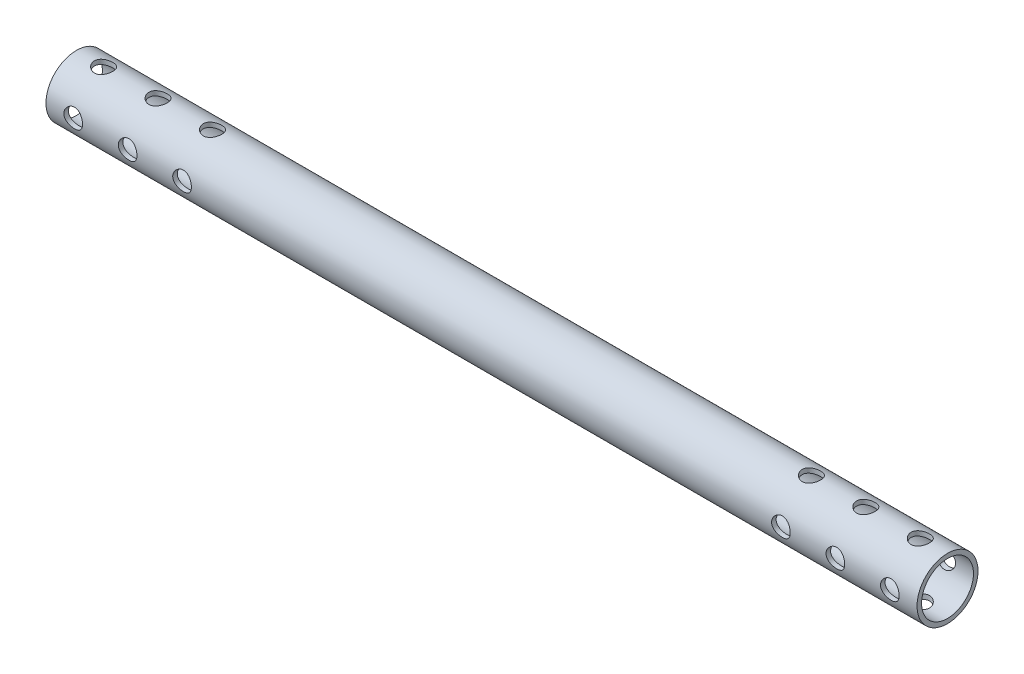
SolidWorks part; units mm, degrees
ref_plane "Front Plane" through (0, 0, 0) normal (0, 0, 1) x (1, 0, 0)
ref_plane "Top Plane" through (0, 0, 0) normal (0, 1, 0) x (1, 0, 0)
ref_plane "Right Plane" through (0, 0, 0) normal (1, 0, 0) x (0, 0, -1)
sketch "Sketch1" plane through (0, 0, 0) normal (1, 0, 0) x (0, 0, -1)
  circle A0 centre (0, 0) radius 10.668
  circle A1 centre (0, 0) radius 9.0805
  dimension "D1" = 1.5875
  dimension "D2" = 21.336
extrude "Boss-Extrude1" add sketch "Sketch1" along normal blind 304.8
ref_plane "Plane1" through (0, 0, 10) normal (0, 0, 1) x (1, 0, 0)
sketch "Sketch2" plane through (0, 0, 10) normal (0, 0, 1) x (1, 0, 0)
  line L0 (0, 0) -> (304.8, 0) construction
  line L1 (304.8, -10.668) -> (304.8, 10.668) construction
  line L2 (152.4, 10.668) -> (152.4, -10.668) construction
  line L3 (304.8, 10.668) -> (0, 10.668) construction
  circle A0 centre (9.525, 0) radius 3.2639
  circle A1 centre (28.575, 0) radius 3.2639
  circle A2 centre (47.625, 0) radius 3.2639
  circle A3 centre (295.275, 0) radius 3.2639
  circle A4 centre (276.225, 0) radius 3.2639
  circle A5 centre (257.175, 0) radius 3.2639
  point P15 (152.4, 0)
  dimension "D1" = 9.525
  dimension "D2" = 3
extrude "Cut-Extrude1" cut sketch "Sketch2" against normal through all and the other way through all
sketch "Sketch3" plane through (0, 0, 0) normal (0, 1, 0) x (1, 0, 0)
  line L0 (304.8, -10.668) -> (304.8, 10.668) construction
  line L1 (152.4, -10.668) -> (152.4, 32.6915) construction
  line L2 (50.8889, -10.668) -> (253.9111, -10.668) construction
  circle A0 centre (295.275, 0) radius 3.2217
  circle A1 centre (276.225, 0) radius 3.2217
  circle A2 centre (257.175, 0) radius 3.2217
  circle A3 centre (47.625, 0) radius 3.2217
  circle A4 centre (28.575, 0) radius 3.2217
  circle A5 centre (9.525, 0) radius 3.2217
  dimension "D2" = 9.525
  dimension "D1" = 3
extrude "Cut-Extrude2" cut sketch "Sketch3" against normal through all both and the other way through all
equation "\"1f\"=10"
